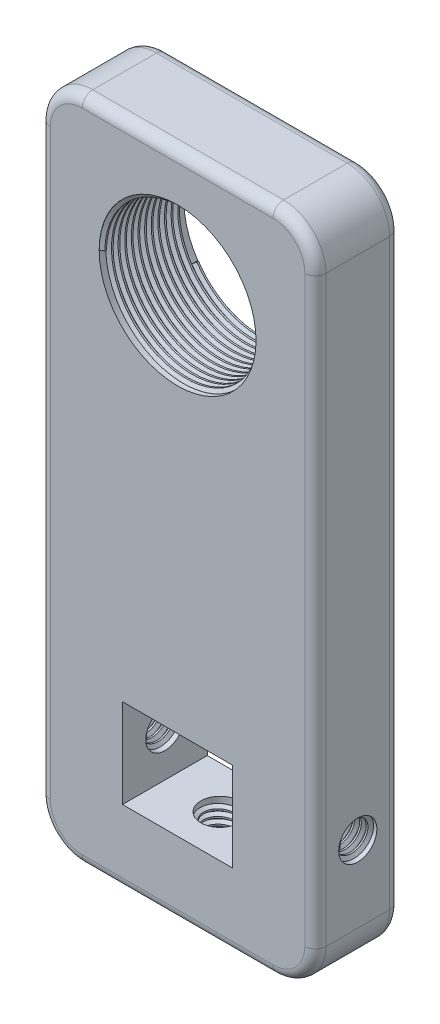
SolidWorks part; units mm, degrees
ref_plane "Front Plane" through (0, 0, 0) normal (0, 0, 1) x (1, 0, 0)
ref_plane "Top Plane" through (0, 0, 0) normal (0, 1, 0) x (1, 0, 0)
ref_plane "Right Plane" through (0, 0, 0) normal (1, 0, 0) x (0, 0, -1)
sketch "Sketch1" plane through (0, 0, 0) normal (0, 0, 1) x (1, 0, 0)
  line L2 (0, 0) -> (0, 66.04)
  line L3 (5.08, 71.12) -> (27.94, 71.12)
  line L4 (33.02, 0) -> (33.02, 66.04)
  line L5 (9.906, 0) -> (9.906, 10.668)
  line L6 (9.906, 10.668) -> (23.114, 10.668)
  line L7 (23.114, 10.668) -> (23.114, 0)
  line L11 (0, 0) -> (0, -3.81)
  line L12 (5.08, -8.89) -> (27.94, -8.89)
  line L13 (33.02, -3.81) -> (33.02, 0)
  line L14 (9.906, 0) -> (23.114, 0)
  line L15 (16.51, 71.12) -> (16.51, 56.134) construction
  line L16 (16.51, 56.134) -> (16.51, 25.654) construction
  line L17 (16.51, 10.668) -> (16.51, 25.654) construction
  line L18 (16.51, 0) -> (16.51, -8.89) construction
  line L19 (0, 10.668) -> (33.02, 10.668) construction
  arc A3 (0, -3.81) -> (5.08, -8.89) centre (5.08, -3.81) ccw
  arc A4 (27.94, -8.89) -> (33.02, -3.81) centre (27.94, -3.81) ccw
  arc A5 (27.94, 71.12) -> (33.02, 66.04) centre (27.94, 66.04) cw
  arc A6 (0, 66.04) -> (5.08, 71.12) centre (5.08, 66.04) cw
  circle A8 centre (16.51, 56.134) radius 9.398
  point P16 (16.51, 71.12)
  point P27 (0, 71.12)
  dimension "D5" = 18.796
  dimension "D7" = 5.08
  dimension "D6" = 9.906
  dimension "D1" = 13.208
  dimension "D2" = 71.12
  dimension "D3" = 10.668
  dimension "D4" = 8.89
extrude "Boss-Extrude2" add sketch "Sketch1" along normal blind 10.16
sketch "Sketch4" plane through (0, 0, 0) normal (-1, 0, 0) x (0, 0, 1)
  circle A0 centre (5.08, 5.334) radius 2.286
  dimension "D1" = 4.572
  dimension "D2" = 5.334
extrude "Cut-Extrude1" cut sketch "Sketch4" against normal blind 38.1
sketch "Sketch6" plane through (0, -8.89, 0) normal (0, -1, 0) x (1, 0, 0)
  line L0 (16.51, 5.08) -> (16.51, 10.16) construction
  line L1 (5.08, 10.16) -> (27.94, 10.16) construction
  line L2 (16.51, 5.08) -> (27.94, 5.08) construction
  line L3 (27.94, 10.16) -> (27.94, 0) construction
  circle A0 centre (16.51, 5.08) radius 2.286
  dimension "D1" = 4.572
extrude "Cut-Extrude2" cut sketch "Sketch6" against normal blind 10.16
thread "Thread1" pitch 0.7937 method extrude profile "Thread Profile1" start angle 0, offset 0, length 9.4488, pitch 0.7937, diameter 18.796
ref_plane "Plane1" through (7.112, 56.134, 10.16) normal (0, -1, 0) x (-1, 0, 0)
sketch "Thread Profile1" plane through (7.112, 56.134, 10.16) normal (0, -1, 0) x (-1, 0, 0)
  line L0 (0, 0) -> (0, 0.7937) construction
  line L11 (0, 0) -> (0, 0.6945)
  line L12 (0, 0.6945) -> (-0.4296, 0.4465)
  line L13 (-0.4296, 0.4465) -> (-0.4296, 0.248)
  line L15 (-0.4296, 0.248) -> (0, 0)
  line L17 (-0.4296, 0.3473) -> (0, 0.3473) construction
  point P2 (0, 0)
  dimension "Pitch" = 0.7937
  dimension "Profile_Angle" = 60
  dimension "Profile_Land" = 0.1984
  dimension "Profile_Height" = 0.4296
thread "Thread2" pitch 0.7937 method extrude profile "Thread Profile2" start angle 0, offset 0, length 9.144, pitch 0.7937, diameter 4.572
ref_plane "Plane2" through (0, 5.334, 2.794) normal (0, -1, 0) x (0, 0, -1)
sketch "Thread Profile2" plane through (0, 5.334, 2.794) normal (0, -1, 0) x (0, 0, -1)
  line L0 (0, 0) -> (0, 0.7937) construction
  line L11 (0, 0) -> (0, 0.6945)
  line L12 (0, 0.6945) -> (-0.4296, 0.4465)
  line L13 (-0.4296, 0.4465) -> (-0.4296, 0.248)
  line L15 (-0.4296, 0.248) -> (0, 0)
  line L17 (-0.4296, 0.3473) -> (0, 0.3473) construction
  point P2 (0, 0)
  dimension "Pitch" = 0.7937
  dimension "Profile_Angle" = 60
  dimension "Profile_Land" = 0.1984
  dimension "Profile_Height" = 0.4296
thread "Thread3" pitch 0.7937 method extrude profile "Thread Profile3" start angle 0, offset 0, length 9.144, pitch 0.7937, diameter 4.572
ref_plane "Plane3" through (33.02, 5.334, 7.366) normal (0, -1, 0) x (0, 0, 1)
sketch "Thread Profile3" plane through (33.02, 5.334, 7.366) normal (0, -1, 0) x (0, 0, 1)
  line L0 (0, 0) -> (0, 0.7937) construction
  line L11 (0, 0) -> (0, 0.6945)
  line L12 (0, 0.6945) -> (-0.4296, 0.4465)
  line L13 (-0.4296, 0.4465) -> (-0.4296, 0.248)
  line L15 (-0.4296, 0.248) -> (0, 0)
  line L17 (-0.4296, 0.3473) -> (0, 0.3473) construction
  point P2 (0, 0)
  dimension "Pitch" = 0.7937
  dimension "Profile_Angle" = 60
  dimension "Profile_Land" = 0.1984
  dimension "Profile_Height" = 0.4296
thread "Thread4" pitch 0.7937 method extrude profile "Thread Profile4" start angle 0, offset 0, length 8.128, pitch 0.7937, diameter 4.572
ref_plane "Plane4" through (18.796, -8.89, 5.08) normal (0, 0, 1) x (1, 0, 0)
sketch "Thread Profile4" plane through (18.796, -8.89, 5.08) normal (0, 0, 1) x (1, 0, 0)
  line L0 (0, 0) -> (0, 0.7937) construction
  line L11 (0, 0) -> (0, 0.6945)
  line L12 (0, 0.6945) -> (-0.4296, 0.4465)
  line L13 (-0.4296, 0.4465) -> (-0.4296, 0.248)
  line L15 (-0.4296, 0.248) -> (0, 0)
  line L17 (-0.4296, 0.3473) -> (0, 0.3473) construction
  point P2 (0, 0)
  dimension "Pitch" = 0.7937
  dimension "Profile_Angle" = 60
  dimension "Profile_Land" = 0.1984
  dimension "Profile_Height" = 0.4296
fillet "Fillet1" radius 1.27 16 edges at (1.4879, 69.6321, 10.16) (0, 31.115, 10.16) (1.4879, -7.4021, 10.16) (16.51, -8.89, 10.16) (31.5321, -7.4021, 10.16) (33.02, 31.115, 10.16) (31.5321, 69.6321, 10.16) (16.51, 71.12, 10.16) (1.4879, 69.6321, 0) (31.5321, 69.6321, 0) (16.51, 71.12, 0) (0, 31.115, 0) (31.5321, -7.4021, 0) (33.02, 31.115, 0) (1.4879, -7.4021, 0) (16.51, -8.89, 0)
